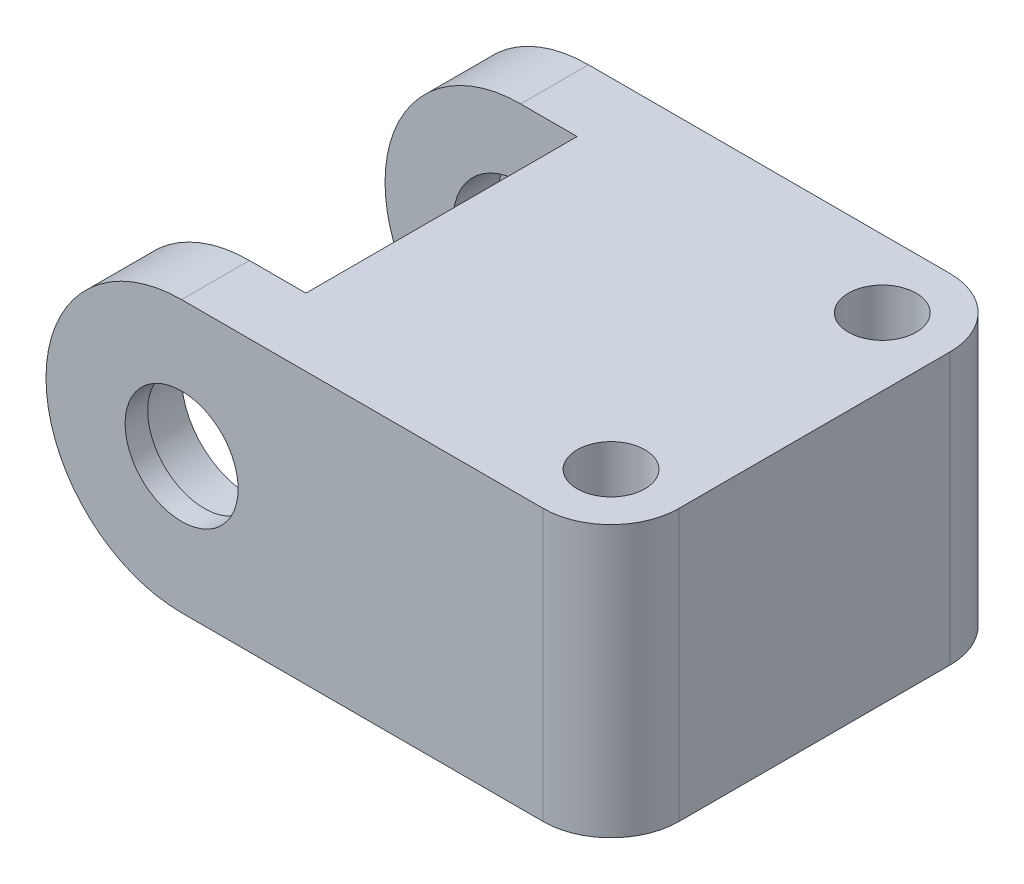
SolidWorks part; units mm, degrees
ref_plane "Front Plane" through (0, 0, 0) normal (0, 0, 1) x (1, 0, 0)
ref_plane "Top Plane" through (0, 0, 0) normal (0, 1, 0) x (1, 0, 0)
ref_plane "Right Plane" through (0, 0, 0) normal (1, 0, 0) x (0, 0, -1)
sketch "Sketch1" plane through (0, 0, 0) normal (0, 0, 1) x (1, 0, 0)
  circle A1 centre (0, 0) radius 6
  circle A2 centre (0, 0) radius 2.5
  point P2 (0, 0)
  dimension "D2" = 5
  dimension "D3" = 12
extrude "Boss-Extrude1" add sketch "Sketch1" along normal mid plane 18
sketch "Sketch2" plane through (0, 0, 0) normal (0, 1, 0) x (1, 0, 0)
  line L0 (0, 9) -> (16, 9)
  line L1 (6, 9) -> (-6, 9) construction
  line L2 (19, 6) -> (19, -6)
  line L3 (16, -9) -> (0, -9)
  line L4 (-6, -9) -> (6, -9) construction
  line L5 (0, -9) -> (0, 9)
  arc A2 (16, 9) -> (19, 6) centre (16, 6) cw
  arc A3 (19, -6) -> (16, -9) centre (16, -6) cw
  circle A4 centre (16, 6) radius 1.5
  circle A5 centre (16, -6) radius 1.5
  dimension "D1" = 16
  dimension "D2" = 3
  dimension "D3" = 3
extrude "Boss-Extrude2" add sketch "Sketch2" along normal mid plane 12
sketch "Sketch3" plane through (0, 0, 0) normal (0, 1, 0) x (1, 0, 0)
  line L0 (0, 12.2341) -> (0, -14.1605) construction
  line L1 (2.5, 8) -> (2.5, 9)
  line L2 (16, 9) -> (0, 9) construction
  line L4 (2.5, 8) -> (3, 8)
  line L5 (3, 8) -> (3, 6)
  line L6 (3, 6) -> (4.5, 6)
  line L8 (4.5, -6) -> (3, -6)
  line L9 (3, -6) -> (3, -8)
  line L10 (3, -8) -> (2.5, -8)
  line L11 (0, -9) -> (0, 9)
  line L12 (0, 9) -> (-2.5, 9) construction
  line L13 (0, 0) -> (-16.9033, 0) construction
  line L16 (2.5, 9) -> (0, 9)
  line L17 (2.5, -8) -> (2.5, -9)
  line L18 (2.5, -9) -> (0, -9)
  line L19 (4.5, 6) -> (4.5, -6)
  point P2 (0, 0)
  point P5 (0, 0)
  point P6 (0, 0)
  dimension "D1" = 6
  dimension "D2" = 1
  dimension "D3" = 2
  dimension "D6" = 0.5
  dimension "D7" = 9
revolve "Cut-Revolve1" cut sketch "Sketch3" angle 360 about L0
sketch "Sketch5" plane through (0, 0, 0) normal (0, 1, 0) x (1, 0, 0)
  line L0 (2.5, 6) -> (2.5, -6)
  line L1 (2.5, -6) -> (-6, -6)
  line L2 (-6, -6) -> (-6, 6)
  line L3 (-6, 6) -> (2.5, 6)
  line L4 (-6, 9) -> (-6, -9) construction
  line L5 (-3, 6) -> (3, 6) construction
  line L6 (0, 9) -> (0, -9) construction
  line L7 (0, 0) -> (-13.9863, 0) construction
  dimension "D1" = 2.5
extrude "Cut-Extrude2" cut sketch "Sketch5" against normal through all both and the other way through all
ref_axis "Axis2" through (0, 0, 11.4241) along (0, 0, -1)
